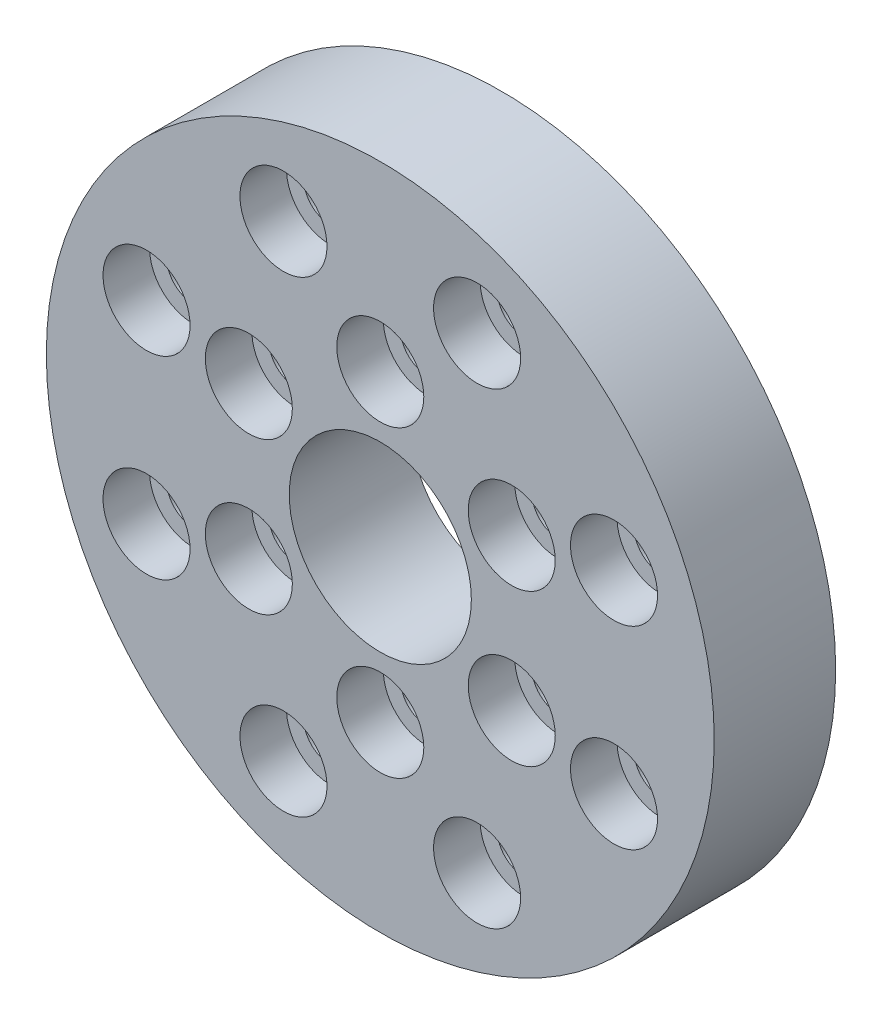
SolidWorks part; units mm, degrees
ref_plane "前视基准面" through (0, 0, 0) normal (0, 0, 1) x (1, 0, 0)
ref_plane "上视基准面" through (0, 0, 0) normal (0, 1, 0) x (1, 0, 0)
ref_plane "右视基准面" through (0, 0, 0) normal (1, 0, 0) x (0, 0, -1)
sketch "草图1" plane through (0, 0, 0) normal (0, 0, 1) x (1, 0, 0)
  circle A0 centre (0, 0) radius 4.5
  circle A1 centre (0, 0) radius 16.5
  dimension "D1" = 33
  dimension "D2" = 9
extrude "凸台-拉伸1" add sketch "草图1" along normal blind 6
hole_wizard "打孔尺寸(%根据)内六角圆柱头螺钉的类型1" positions "草图6" profile "草图5" counterbore size "M2" standard "GB" end condition through all
sketch "草图6" plane through (0, 0, 6) normal (0, 0, 1) x (1, 0, 0)
  line L0 (0, 0) -> (0, 18.5232) construction
  circle A0 centre (0, 0) radius 7.5 construction
  point P0 (0, 7.5)
  dimension "D1" = 15
sketch "草图5" plane through (0, 7.5, 6) normal (1, 0, 0) x (0, -1, 0)
  line L0 (0, 0) -> (0, 6)
  line L1 (0, 6) -> (1.3, 6)
  line L3 (1.3, 6) -> (1.3, 2.3)
  line L4 (1.3, 2.3) -> (2.15, 2.3)
  line L5 (2.15, 2.3) -> (2.15, 0)
  line L7 (2.15, 0) -> (0, 0)
  line L11 (0, -6.35) -> (0, 107.95) construction
  dimension "通孔孔直径" = 2.6
  dimension "通孔孔深度" = 6
  dimension "柱形沉头孔直径" = 4.3
  dimension "柱形沉头孔深度" = 2.3
ref_axis "基准轴1" through (0, 0, 6) along (0, 0, -1)
pattern_circular "阵列(圆周)1" count 6 over 360 about axis through (0, 0, 6) along (0, 0, -1) of "打孔尺寸(%根据)内六角圆柱头螺钉的类型1"
hole_wizard "打孔尺寸(%根据)内六角圆柱头螺钉的类型2" positions "草图8" profile "草图7" counterbore size "M2" standard "GB" end condition through all
sketch "草图8" plane through (0, 0, 6) normal (0, 0, 1) x (1, 0, 0)
  line L0 (0, 0) -> (0, 19.0524) construction
  line L2 (0, 0) -> (-7.6063, 18.3632) construction
  circle A0 centre (0, 0) radius 12.5 construction
  point P0 (-4.7835, 11.5485)
  dimension "D2" = 25
  dimension "D1" = 22.5
sketch "草图7" plane through (-4.7835, 11.5485, 6) normal (1, 0, 0) x (0, -1, 0)
  line L0 (0, 0) -> (0, 6)
  line L1 (0, 6) -> (1.3, 6)
  line L3 (1.3, 6) -> (1.3, 2.3)
  line L4 (1.3, 2.3) -> (2.15, 2.3)
  line L5 (2.15, 2.3) -> (2.15, 0)
  line L7 (2.15, 0) -> (0, 0)
  line L11 (0, -6.35) -> (0, 107.95) construction
  dimension "通孔孔直径" = 2.6
  dimension "通孔孔深度" = 6
  dimension "柱形沉头孔直径" = 4.3
  dimension "柱形沉头孔深度" = 2.3
pattern_circular "阵列(圆周)2" count 8 over 360 about axis through (0, 0, 6) along (0, 0, -1) of "打孔尺寸(%根据)内六角圆柱头螺钉的类型2"
